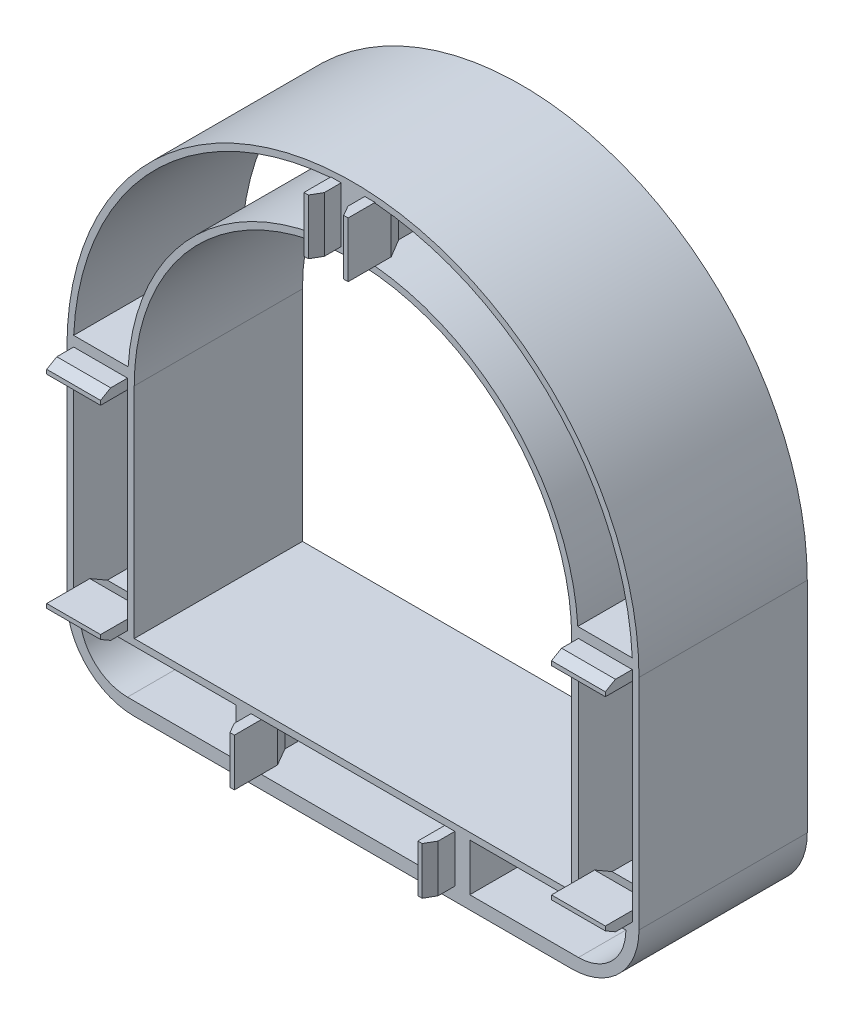
SolidWorks part; units mm, degrees
ref_plane "Alzado" through (0, 0, 0) normal (0, 0, 1) x (1, 0, 0)
ref_plane "Planta" through (0, 0, 0) normal (0, 1, 0) x (1, 0, 0)
ref_plane "Vista lateral" through (0, 0, 0) normal (1, 0, 0) x (0, 0, -1)
sketch "Croquis1" plane through (0, 0, 0) normal (0, 0, 1) x (1, 0, 0)
  line L0 (83, -63.9768) -> (83, 1.0232)
  line L1 (-65, -65) -> (65, -65)
  line L2 (-85, 0) -> (-85, -65)
  line L3 (-65, -85) -> (65, -85)
  line L4 (85, 0) -> (85, -65)
  line L5 (-65, -65) -> (-65, 0)
  line L6 (-83, -63.9768) -> (-67, -63.9768)
  line L7 (65, -65) -> (65, 0)
  line L8 (-83, -63.9768) -> (-83, 1.0232)
  line L9 (-83, 1.0232) -> (-67, 1.0232)
  line L10 (-67, -63.9768) -> (-67, 1.0232)
  line L11 (67, -63.9768) -> (67, 1.0232)
  line L12 (67, -63.9768) -> (83, -63.9768)
  line L13 (67, 1.0232) -> (83, 1.0232)
  line L14 (3.5102, 83.0233) -> (3.5102, 66.8394)
  line L15 (66.8105, 4.0232) -> (83, 4.0232)
  line L17 (-66.8105, 4.0232) -> (-83, 4.0232)
  line L18 (-3.5102, 83.0233) -> (-3.5102, 66.8394)
  line L19 (-81.0966, -66.9768) -> (-34.7159, -66.9768)
  line L21 (67, -81.0734) -> (34.7159, -81.0734)
  line L22 (-34.7159, -81.0734) -> (-34.7159, -66.9768)
  line L23 (34.7159, -66.9768) -> (81.0966, -66.9768)
  line L24 (-34.7159, -81.0734) -> (-67, -81.0734)
  line L25 (-30.2841, -81.0734) -> (-30.2841, -66.9768)
  line L26 (30.2841, -81.0734) -> (-30.2841, -81.0734)
  line L28 (30.2841, -81.0734) -> (30.2841, -66.9768)
  line L31 (34.7159, -81.0734) -> (34.7159, -66.9768)
  line L34 (-30.2841, -66.9768) -> (30.2841, -66.9768)
  arc A0 (85, 0) -> (-85, 0) centre (0, 0) ccw
  arc A1 (65, -85) -> (85, -65) centre (65, -65) ccw
  arc A2 (-85, -65) -> (-65, -85) centre (-65, -65) ccw
  arc A3 (65, 0) -> (-65, 0) centre (0, 0) ccw
  arc A4 (83, 4.0232) -> (3.5102, 83.0233) centre (0, 0) ccw
  arc A5 (-83, 4.0232) -> (-3.5102, 83.0233) centre (0, 0) cw
  arc A6 (66.8105, 4.0232) -> (3.5102, 66.8394) centre (0, 0) ccw
  arc A7 (-66.8105, 4.0232) -> (-3.5102, 66.8394) centre (0, 0) cw
  arc A8 (-81.0966, -66.9768) -> (-67, -81.0734) centre (-67, -66.9768) ccw
  arc A9 (81.0966, -66.9768) -> (67, -81.0734) centre (67, -66.9768) cw
  point P36 (32.5, -74.2969)
  point P38 (-32.5, -74.2969)
  dimension "D1" = 65
  dimension "D2" = 65
  dimension "D4" = 3
  dimension "D5" = 3
extrude "Saliente-Extruir1" add sketch "Croquis1" along normal blind 50
ref_plane "Plano1" through (0, 0, 40) normal (0, 0, 1) x (1, 0, 0)
sketch "Croquis3" plane through (0, 0, 40) normal (0, 0, 1) x (1, 0, 0)
  line L0 (0, 110.0059) -> (0, -109.6339) construction
  line L1 (-67, -63.9768) -> (-67, 1.0232) construction
  line L2 (-83, 1.0232) -> (-67, 1.0232)
  line L3 (-83, 1.0232) -> (-83, -1.9768)
  line L4 (-83, -1.9768) -> (-67, -1.9768)
  line L5 (-67, 1.0232) -> (-67, -1.9768)
  line L6 (-83, -63.9768) -> (-67, -63.9768)
  line L7 (-83, -60.9768) -> (-83, -63.9768)
  line L8 (-67, -60.9768) -> (-67, -63.9768)
  line L9 (-83, -60.9768) -> (-67, -60.9768)
  line L10 (67, -63.9768) -> (83, -63.9768)
  line L11 (67, -60.9768) -> (67, -63.9768)
  line L12 (83, -60.9768) -> (83, -63.9768)
  line L13 (67, -60.9768) -> (83, -60.9768)
  line L14 (67, -1.9768) -> (83, -1.9768)
  line L15 (67, 1.0232) -> (67, -1.9768)
  line L16 (83, 1.0232) -> (83, -1.9768)
  line L17 (67, 1.0232) -> (83, 1.0232)
  line L18 (-3.5102, 66.8394) -> (-3.5102, 83.0233) construction
  line L19 (-3.5102, 83.0233) -> (-6.5635, 83.0233)
  line L20 (-3.5102, 83.0233) -> (-3.5102, 66.6089)
  line L21 (-3.5102, 66.6089) -> (-6.5635, 66.6089)
  line L22 (-6.5635, 83.0233) -> (-6.5635, 66.6089)
  line L23 (-30.2841, -81.0734) -> (30.2841, -81.0734) construction
  line L24 (3.5102, 83.0233) -> (6.5635, 83.0233)
  line L25 (3.5102, 83.0233) -> (3.5102, 66.6089)
  line L26 (3.5102, 66.6089) -> (6.5635, 66.6089)
  line L27 (6.5635, 83.0233) -> (6.5635, 66.6089)
  line L28 (-30.2841, -66.9768) -> (-27.2391, -66.9768)
  line L29 (-30.2841, -66.9768) -> (-30.2841, -81.0734)
  line L30 (-30.2841, -81.0734) -> (-27.2391, -81.0734)
  line L31 (-27.2391, -66.9768) -> (-27.2391, -81.0734)
  line L33 (30.2841, -66.9768) -> (27.2597, -66.9768)
  line L34 (30.2841, -66.9768) -> (30.2841, -81.0734)
  line L35 (30.2841, -81.0734) -> (27.2597, -81.0734)
  line L36 (27.2597, -66.9768) -> (27.2597, -81.0734)
  arc A0 (-3.5102, 83.0233) -> (-83, 4.0232) centre (0, 0) ccw construction
  arc A1 (-3.5102, 66.8394) -> (-66.8105, 4.0232) centre (0, 0) ccw construction
  arc A2 (66.8105, 4.0232) -> (3.5102, 66.8394) centre (0, 0) ccw construction
extrude "Saliente-Extruir2" add sketch "Croquis3" along normal blind 18
chamfer "Chaflán2" distance 3 angle 30 8 edges at (30.2841, -74.0251, 58) (-30.2841, -74.0251, 58) (-75, -63.9768, 58) (75, -63.9768, 58) (75, 1.0232, 58) (-75, 1.0232, 58) (3.5102, 74.8161, 58) (-3.5102, 74.8161, 58) first distance on face at (30.2841, -74.0251, 54) first distance on face at (-30.2841, -74.0251, 54) first distance on face at (-75, -63.9768, 54) first distance on face at (75, -63.9768, 54) first distance on face at (75, 1.0232, 54) first distance on face at (-75, 1.0232, 54) first distance on face at (3.5102, 74.8161, 54) first distance on face at (-3.5102, 74.8161, 54)
chamfer "Chaflán3" distance 3 angle 60 8 edges at (75, -60.9768, 40) (75, -1.9768, 40) (27.2597, -74.0251, 40) (-27.2391, -74.0251, 40) (-75, -60.9768, 40) (-75, -1.9768, 40) (-6.5635, 74.7234, 40) (6.5635, 74.7234, 40) first distance on face at (75, -62.4768, 40) first distance on face at (75, -0.4768, 40) first distance on face at (28.7719, -74.0251, 40) first distance on face at (-28.7616, -74.0251, 40) first distance on face at (-75, -62.4768, 40) first distance on face at (-75, -0.4768, 40) first distance on face at (-5.0374, 74.8352, 40) first distance on face at (5.0374, 74.8352, 40)
